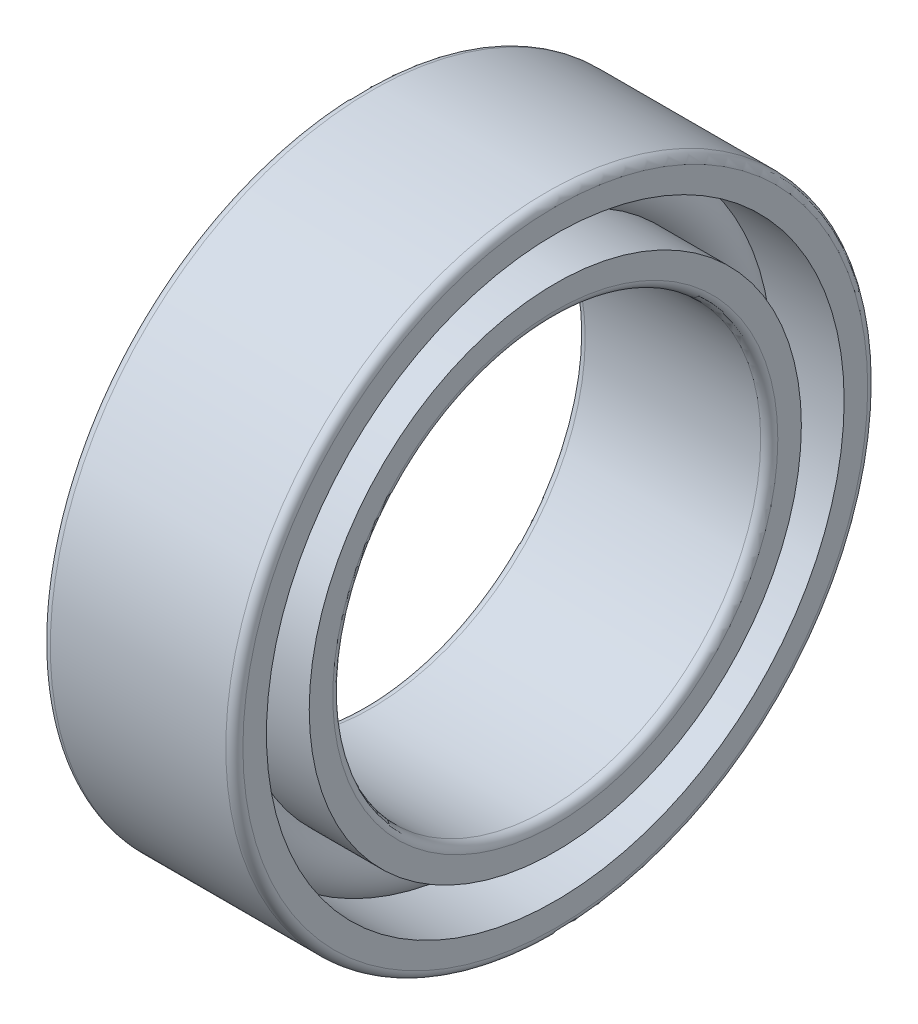
SolidWorks part; units mm, degrees
ref_plane "Plane1" through (0, 0, 0) normal (0, 0, 1) x (1, 0, 0)
ref_plane "Plane2" through (0, 0, 0) normal (0, 1, 0) x (1, 0, 0)
ref_plane "Plane3" through (0, 0, 0) normal (1, 0, 0) x (0, 0, -1)
other "Configuration Table"
sketch "Clipboard" plane through (0, 0, 0) normal (0, 0, 1) x (1, 0, 0)
  line L0 (-10, 0) -> (10, 0) construction
  line L1 (0, 0) -> (22.3471, -0.7804)
  line L2 (0, 0) -> (6.2462, 0.2181)
  line L3 (0, 0) -> (22.3471, -0.7804)
  line L4 (0, 0) -> (-22.3573, -0.3902)
sketch "CagSpiSke" plane through (0, 0, 0) normal (0, 0, 1) x (1, 0, 0)
  line L0 (0.075, 6.125) -> (0.075, 6.375)
  line L1 (0.075, 6.375) -> (-0.075, 6.375)
  line L2 (-0.075, 6.375) -> (-0.075, 6.125)
  line L3 (-0.075, 6.125) -> (0.075, 6.125)
  line L4 (-20.6375, 0) -> (20.6375, 0) construction
  line L5 (0, 0) -> (0, 23.7692) construction
revolve "CageSpine" add sketch "CagSpiSke" angle 0.001 about L4 reverse direction yes
ref_axis "Axis1" through (-50, 0, 0) along (1, 0, 0)
sketch "CagBalSke" plane through (0, 0, 0) normal (0, 0, 1) x (1, 0, 0)
  line L0 (-0.825, 6.25) -> (0.825, 6.25)
  line L1 (-1.905, 6.25) -> (1.905, 6.25) construction
  line L2 (-10, 0) -> (10, 0) construction
  line L3 (0, 0) -> (0, 24) construction
  arc A0 (0.825, 6.25) -> (-0.825, 6.25) centre (0, 6.25) cw
revolve "CageBall" [suppressed] add sketch "CagBalSke" angle 360 about L1 reverse direction yes
pattern_circular "CageBalls" [suppressed] count 2 every 180 about axis through (-50, 0, 0) along (1, 0, 0)
sketch "CagTrmODSke" plane through (0, 0, 0) normal (0, 0, 1) x (1, 0, 0)
  line L0 (0.826, 6.375) -> (0.826, 7.076)
  line L1 (0.826, 7.076) -> (-0.826, 7.076)
  line L2 (-0.826, 7.076) -> (-0.826, 6.375)
  line L3 (-0.826, 6.375) -> (0.826, 6.375)
  line L4 (-20.6375, 0) -> (20.6375, 0) construction
  line L5 (0, 0) -> (0, 25) construction
revolve "CageTrimOD" [suppressed] cut sketch "CagTrmODSke" angle 360 about L4 reverse direction yes
sketch "CagTrmIDSke" plane through (0, 0, 0) normal (0, 0, 1) x (1, 0, 0)
  line L0 (0.826, 5.426) -> (0.826, 6.125)
  line L1 (0.826, 6.125) -> (-0.826, 6.125)
  line L2 (-0.826, 6.125) -> (-0.826, 5.426)
  line L3 (-0.826, 5.426) -> (0.826, 5.426)
  line L4 (-20.6375, 0) -> (20.6375, 0) construction
  line L5 (0, 0) -> (0, 25) construction
revolve "CageTrimID" [suppressed] cut sketch "CagTrmIDSke" angle 360 about L4 reverse direction yes
sketch "BalSimSke" plane through (0, 0, 0) normal (0, 0, 1) x (1, 0, 0)
  line L0 (-10, 0) -> (10, 0) construction
  line L1 (-10, 6.25) -> (10, 6.25) construction
  line L2 (0, 0) -> (0, 23) construction
  circle A0 centre (0, 6.25) radius 0.75
revolve "BallsSimplified" add sketch "BalSimSke" angle 360 about L0
sketch "BalDetSke" plane through (0, 0, 0) normal (0, 0, 1) x (1, 0, 0)
  line L0 (-0.75, 6.25) -> (0.75, 6.25)
  line L1 (-1.905, 6.25) -> (1.905, 6.25) construction
  line L2 (0, 0) -> (0, 25) construction
  arc A0 (0.75, 6.25) -> (-0.75, 6.25) centre (0, 6.25) cw
revolve "BallDetailed" [suppressed] add sketch "BalDetSke" angle 360 about L1 reverse direction yes
sketch "InnRacSke" plane through (0, 0, 0) normal (0, 0, 1) x (1, 0, 0)
  line L0 (-0.525, 5.75) -> (-2.25, 5.75)
  line L1 (-2.25, 5.75) -> (-2.25, 5.2)
  line L2 (-2.05, 5) -> (2.05, 5)
  line L3 (2.25, 5.2) -> (2.25, 5.75)
  line L4 (2.25, 5.75) -> (0.525, 5.75)
  line L5 (-20.6375, 0) -> (20.6375, 0) construction
  line L6 (0, 0) -> (0, 30) construction
  arc A0 (-2.25, 5.2) -> (-2.05, 5) centre (-2.05, 5.2) ccw
  arc A1 (2.05, 5) -> (2.25, 5.2) centre (2.05, 5.2) ccw
  arc A2 (0.525, 5.75) -> (-0.525, 5.75) centre (0, 6.25) cw
revolve "InnerRace" add sketch "InnRacSke" angle 360 about L5 reverse direction yes
sketch "OutRacSke" plane through (0, 0, 0) normal (0, 0, 1) x (1, 0, 0)
  line L0 (-0.525, 6.75) -> (-2.25, 6.75)
  line L1 (-2.25, 6.75) -> (-2.25, 7.3)
  line L2 (-2.05, 7.5) -> (2.05, 7.5)
  line L3 (2.25, 7.3) -> (2.25, 6.75)
  line L4 (2.25, 6.75) -> (0.525, 6.75)
  line L5 (-20.6375, 0) -> (20.6375, 0) construction
  line L6 (0, 0) -> (0, 30) construction
  arc A0 (-2.25, 7.3) -> (-2.05, 7.5) centre (-2.05, 7.3) cw
  arc A1 (2.05, 7.5) -> (2.25, 7.3) centre (2.05, 7.3) cw
  arc A2 (0.525, 6.75) -> (-0.525, 6.75) centre (0, 6.25) ccw
revolve "OuterRace" add sketch "OutRacSke" angle 360 about L5 reverse direction yes
pattern_circular "BallsDetailed" [suppressed] count 2 every 180 about axis through (-50, 0, 0) along (1, 0, 0)
equation "\"BallCLRad@Clipboard\" = ( \"OD@OutRacSke\" + \"ID@InnRacSke\" ) / 4"
equation "\"BallCLRad@BalSimSke\" = \"BallCLRad@Clipboard\""
equation "\"BallCLRad@BalDetSke\" = \"BallCLRad@Clipboard\""
equation "\"BallCLRad@InnRacSke\" = \"BallCLRad@Clipboard\""
equation "\"BallCLRad@OutRacSke\" = \"BallCLRad@Clipboard\""
equation "\"Ball_diameter@InnRacSke\" = \"Ball_diameter@BalDetSke\" - 0.05"
equation "\"Ball_diameter@OutRacSke\" = \"Ball_diameter@BalDetSke\" - 0.05"
equation "\"Ball_diameter@BalSimSke\" = \"Ball_diameter@BalDetSke\""
equation "\"Width@OutRacSke\" = \"Width@InnRacSke\""
equation "\"Fillet_radius@OutRacSke\" = \"Fillet_radius@InnRacSke\""
equation "\"Max_count@Clipboard\" = int( 3.14159265 / atn(( \"Ball_diameter@BalDetSke\" / 2) / sqr( \"BallCLRad@Clipboard\"  *  \"BallCLRad@Clipboard\" - ( \"Ball_diameter@BalDetSke\" / 2) *  ( \"Ball_diameter@BalDetSke\" / 2))))"
equation "\"Max_count@Clipboard\" = ((sgn( \"Max_count@Clipboard\" - \"Count@Clipboard\" )-1)*( \"Max_count@Clipboard\" - \"Count@Clipboard\" ))/-2+ \"Count@Clipboard\""
equation "\"Count@BallsDetailed\" = int( \"Show_count@Clipboard\" ) "
equation "\"Count@BallsDetailed\" = ((sgn( \"Count@BallsDetailed\" - \"Max_count@Clipboard\" )-1)*( \"Count@BallsDetailed\" - \"Max_count@Clipboard\" ))/-2+ \"Max_count@Clipboard\""
equation "\"Count@BallsDetailed\" = ((sgn( \"Count@BallsDetailed\" - \"Min_count@Clipboard\" )+1)*( \"Count@BallsDetailed\" - \"Min_count@Clipboard\"))/2 +\"Min_count@Clipboard\""
equation "\"Angle@BallsDetailed\" = 360.0 / \"Max_count@Clipboard\""
equation "\"BallCLRad@CagBalSke\" = \"BallCLRad@Clipboard\""
equation "\"Count@CageBalls\" = \"Count@BallsDetailed\""
equation "\"Angle@CageBalls\" = \"Angle@BallsDetailed\""
equation "\"Angle@CageSpine\" =  \"Angle@CageBalls\" * ( \"Count@CageBalls\" -1 + int( \"Count@CageBalls\" / \"Max_count@Clipboard\" ) )  + 0.001 -  int( \"Count@CageBalls\" / \"Max_count@Clipboard\" ) * 0.001"
equation "\"Angle@CageSpine\" =  \"Angle@CageSpine\" * int( \"Min_count@Clipboard\" / 2) + int(1 / \"Min_count@Clipboard\")  * 0.001"
equation "\"CageWallOD@CagBalSke\" =  \"Ball_diameter@BalDetSke\" * 1.1"
equation "\"Thickness@CagSpiSke\" =  \"Ball_diameter@BalDetSke\" * 0.1"
equation "\"OD@CagTrmODSke\" = \"BallCLRad@Clipboard\" * 2 + \"CageWallOD@CagBalSke\" + 0.002"
equation "\"ID@CagTrmODSke\" = \"BallCLRad@Clipboard\" * 2 + \"Ball_diameter@BalDetSke\" / 6"
equation "\"OD@CagTrmIDSke\" = \"BallCLRad@Clipboard\" * 2 - \"Ball_diameter@BalDetSke\" / 6"
equation "\"ID@CagTrmIDSke\" = \"BallCLRad@Clipboard\" * 2 - \"CageWallOD@CagBalSke\" + 0.002"
equation "\"OD@CagSpiSke\" = \"ID@CagTrmODSke\""
equation "\"ID@CagSpiSke\" = \"OD@CagTrmIDSke\""
equation "\"Width@CagTrmODSke\" = \"CageWallOD@CagBalSke\" + 0.002"
equation "\"Width@CagTrmIDSke\" = \"CageWallOD@CagBalSke\" + 0.002"
